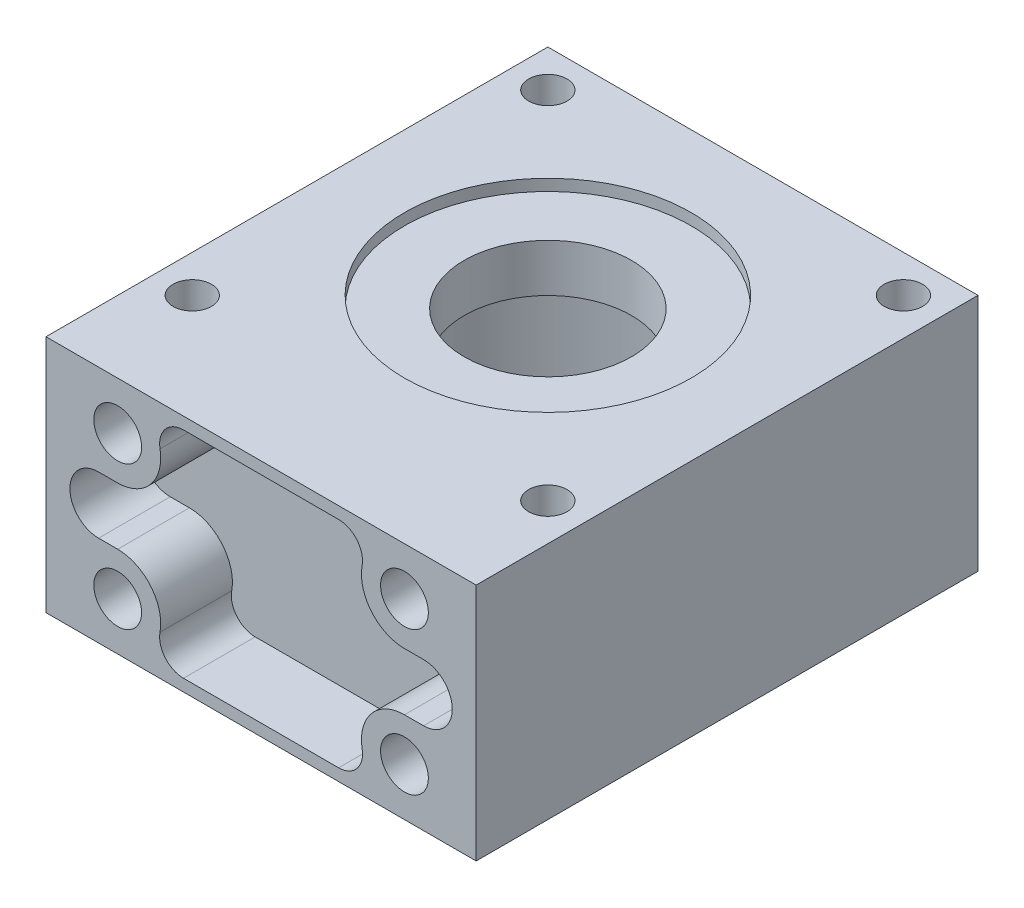
SolidWorks part; units mm, degrees
material "6061 Alloy"
ref_plane "Front" through (0, 0, 0) normal (0, 0, 1) x (1, 0, 0)
ref_plane "Top" through (0, 0, 0) normal (0, 1, 0) x (1, 0, 0)
ref_plane "Right" through (0, 0, 0) normal (1, 0, 0) x (0, 0, -1)
sketch "Sketch1" plane through (0, 0, 0) normal (0, 1, 0) x (1, 0, 0)
  line L0 (28.575, 28.575) -> (-28.575, 28.575)
  line L1 (-28.575, 28.575) -> (28.575, 28.575) construction
  line L2 (-28.575, 28.575) -> (-28.575, -28.575)
  line L3 (-28.575, -28.575) -> (28.575, -28.575) construction
  line L4 (28.575, 28.575) -> (28.575, -28.575)
  line L5 (-28.575, 28.575) -> (28.575, -28.575) construction
  line L6 (-28.575, -28.575) -> (28.575, 28.575) construction
  line L7 (-23.622, 23.622) -> (23.622, 23.622) construction
  line L8 (-23.622, 23.622) -> (-23.622, -23.622) construction
  line L9 (-23.622, -23.622) -> (23.622, -23.622) construction
  line L10 (23.622, 23.622) -> (23.622, -23.622) construction
  line L11 (-23.622, 23.622) -> (23.622, -23.622) construction
  line L12 (-23.622, -23.622) -> (23.622, 23.622) construction
  line L15 (-28.575, -28.575) -> (-28.575, -38.1)
  line L16 (-28.575, -38.1) -> (28.575, -38.1)
  line L17 (28.575, -38.1) -> (28.575, -28.575)
  circle A0 centre (23.622, -23.622) radius 2.5527
  circle A1 centre (23.622, 23.622) radius 2.5527
  circle A2 centre (-23.622, 23.622) radius 2.5527
  circle A3 centre (-23.622, -23.622) radius 2.5527
  point P0 (0, 0)
  point P6 (0, 0)
  dimension "D3" = 5.1054
  dimension "D1" = 57.15
  dimension "D2" = 47.244
  dimension "D4" = 9.525
extrude "Boss-Extrude1" add sketch "Sketch1" along normal blind 31.75
sketch "Sketch2" plane through (0, 31.75, 0) normal (0, 1, 0) x (1, 0, 0)
  circle A0 centre (0, 0) radius 19.05
  dimension "D1" = 38.1
extrude "Cut-Extrude1" cut sketch "Sketch2" against normal blind 1.524
sketch "Sketch3" plane through (0, 30.226, 0) normal (0, 1, 0) x (1, 0, 0)
  circle A0 centre (0, 0) radius 11.1125
  dimension "D1" = 22.225
extrude "Cut-Extrude2" cut sketch "Sketch3" against normal through all
sketch "Sketch4" plane through (0, 0, 0) normal (0, -1, 0) x (1, 0, 0)
  line L0 (0, 0) -> (0, 28.575) construction
  line L2 (0, 0) -> (13.0457, 20.2994) construction
  line L5 (-28.575, 28.575) -> (28.575, 28.575) construction
  circle A0 centre (0, 0) radius 21.844 construction
  circle A1 centre (0, 0) radius 24.13 construction
  arc A2 (0, 20.955) -> (2.8224, 22.6758) centre (0, 24.13) ccw
  arc A3 (11.3291, 17.6285) -> (9.8851, 20.602) centre (13.0457, 20.2994) cw
  arc A4 (2.8224, 22.6758) -> (9.8851, 20.602) centre (6.1542, 20.9592) cw
  arc A5 (11.3291, 17.6285) -> (14.6338, 17.5502) centre (13.0457, 20.2994) ccw
  arc A6 (14.6338, 17.5502) -> (19.4542, 11.9872) centre (16.5086, 14.3048) cw
  arc A7 (19.0613, 8.705) -> (19.4542, 11.9872) centre (21.9494, 10.024) cw
  arc A8 (19.0613, 8.705) -> (21.7991, 6.8525) centre (21.9494, 10.024) ccw
  arc A9 (21.7991, 6.8525) -> (22.8467, -0.4334) centre (21.6217, 3.1087) cw
  arc A10 (20.7417, -2.9822) -> (22.8467, -0.4334) centre (23.8844, -3.4341) cw
  arc A11 (20.7417, -2.9822) -> (22.0433, -6.0208) centre (23.8844, -3.4341) ccw
  arc A12 (22.0433, -6.0208) -> (18.9855, -12.7165) centre (19.87, -9.0743) cw
  arc A13 (15.8367, -13.7226) -> (18.9855, -12.7165) centre (18.2362, -15.8018) cw
  arc A14 (15.8367, -13.7226) -> (15.289, -16.9825) centre (18.2362, -15.8018) ccw
  arc A15 (15.289, -16.9825) -> (9.0966, -20.9621) centre (11.8098, -18.3763) cw
  arc A16 (5.9037, -20.1062) -> (9.0966, -20.9621) centre (6.7982, -23.1526) cw
  arc A17 (5.9037, -20.1062) -> (3.6804, -22.5524) centre (6.7982, -23.1526) ccw
  arc A18 (3.6804, -22.5524) -> (-3.6804, -22.5524) centre (0, -21.844) cw
  arc A19 (-5.9037, -20.1062) -> (-3.6804, -22.5524) centre (-6.7982, -23.1526) cw
  arc A20 (-5.9037, -20.1062) -> (-9.0966, -20.9621) centre (-6.7982, -23.1526) ccw
  arc A21 (-9.0966, -20.9621) -> (-15.289, -16.9825) centre (-11.8098, -18.3763) cw
  arc A22 (-15.8367, -13.7226) -> (-15.289, -16.9825) centre (-18.2362, -15.8018) cw
  arc A23 (-15.8367, -13.7226) -> (-18.9855, -12.7165) centre (-18.2362, -15.8018) ccw
  arc A24 (-18.9855, -12.7165) -> (-22.0433, -6.0208) centre (-19.87, -9.0743) cw
  arc A25 (-20.7417, -2.9822) -> (-22.0433, -6.0208) centre (-23.8844, -3.4341) cw
  arc A26 (-20.7417, -2.9822) -> (-22.8467, -0.4334) centre (-23.8844, -3.4341) ccw
  arc A27 (-22.8467, -0.4334) -> (-21.7991, 6.8525) centre (-21.6217, 3.1087) cw
  arc A28 (-19.0613, 8.705) -> (-21.7991, 6.8525) centre (-21.9494, 10.024) cw
  arc A29 (-19.0613, 8.705) -> (-19.4542, 11.9872) centre (-21.9494, 10.024) ccw
  arc A30 (-19.4542, 11.9872) -> (-14.6338, 17.5502) centre (-16.5086, 14.3048) cw
  arc A31 (-11.3291, 17.6285) -> (-14.6338, 17.5502) centre (-13.0457, 20.2994) cw
  arc A32 (-11.3291, 17.6285) -> (-9.8851, 20.602) centre (-13.0457, 20.2994) ccw
  arc A33 (-9.8851, 20.602) -> (-2.8224, 22.6758) centre (-6.1542, 20.9592) cw
  arc A34 (0, 20.955) -> (-2.8224, 22.6758) centre (0, 24.13) cw
  point P14 (0, 28.575)
  point P87 (0, 0)
  dimension "D1" = 48.26
  dimension "D2" = 43.688
  dimension "D4" = 3.175
  dimension "D5" = 3.175
  dimension "D3" = 32.727
  dimension "D6" = 11
extrude "Cut-Extrude3" cut sketch "Sketch4" against normal blind 23.876
sketch "Sketch5" plane through (0, 0, 0) normal (0, -1, 0) x (1, 0, 0)
  circle A0 centre (0, 0) radius 26.1937
  dimension "D1" = 52.3875
extrude "Cut-Extrude4" cut sketch "Sketch5" against normal blind 17.526
sketch "Sketch7" plane through (0, 0, 0) normal (0, -1, 0) x (1, 0, 0)
  line L0 (-28.575, -28.575) -> (28.575, -28.575) construction
  line L4 (-28.575, -28.575) -> (-28.575, 38.1) construction
  line L5 (-23.8125, 26.9875) -> (23.8125, 26.9875)
  line L6 (-26.9875, 23.8125) -> (-26.9875, -23.8125)
  line L7 (-23.8125, -26.9875) -> (23.8125, -26.9875)
  line L8 (26.9875, 23.8125) -> (26.9875, -23.8125)
  line L9 (-26.9875, 26.9875) -> (26.9875, -26.9875) construction
  line L10 (-26.9875, -26.9875) -> (26.9875, 26.9875) construction
  arc A0 (-26.9875, -23.8125) -> (-23.8125, -26.9875) centre (-23.8125, -23.8125) ccw
  arc A2 (23.8125, -26.9875) -> (26.9875, -23.8125) centre (23.8125, -23.8125) ccw
  arc A3 (23.8125, 26.9875) -> (26.9875, 23.8125) centre (23.8125, 23.8125) cw
  arc A4 (-23.8125, 26.9875) -> (-26.9875, 23.8125) centre (-23.8125, 23.8125) ccw
  point P0 (0, 0)
  dimension "D1" = 1.5875
  dimension "D3" = 3.175
  dimension "D2" = 1.5875
extrude "Cut-Extrude5" cut sketch "Sketch7" against normal blind 1.5875
ref_plane "Plane1" through (0, 0, 28.575) normal (0, 0, 1) x (1, 0, 0)
sketch "Sketch10" plane through (0, 0, 38.1) normal (0, 0, 1) x (1, 0, 0)
  line L0 (28.575, 31.75) -> (28.575, 0) construction
  line L1 (19.05, 25.4) -> (-19.05, 25.4)
  line L2 (19.05, 25.4) -> (19.05, 6.35)
  line L3 (19.05, 6.35) -> (-19.05, 6.35)
  line L4 (-19.05, 25.4) -> (-19.05, 6.35)
  line L5 (19.05, 25.4) -> (-19.05, 6.35) construction
  line L6 (19.05, 6.35) -> (-19.05, 25.4) construction
  line L7 (-28.575, 0) -> (28.575, 0) construction
  point P0 (0, 15.875)
  point P7 (28.575, 15.875)
  point P10 (0, 0)
  dimension "D1" = 38.1
  dimension "D2" = 19.05
hole_wizard "1/4-20 Tapped Hole1" positions "Sketch12" profile "Sketch11" tap size "1/4-20" standard "ANSI Inch"
sketch "Sketch12" plane through (0, 0, 38.1) normal (0, 0, 1) x (1, 0, 0)
  point P0 (-19.05, 25.4)
  point P3 (19.05, 25.4)
  point P6 (19.05, 6.35)
  point P9 (-19.05, 6.35)
sketch "Sketch11" plane through (-19.05, 25.4, 38.1) normal (1, 0, 0) x (0, -1, 0)
  line L0 (0, 0) -> (0, 11.1858)
  line L1 (0, 11.1858) -> (2.5527, 9.652)
  line L2 (2.5527, 9.652) -> (2.5527, 9.525)
  line L3 (2.5527, 9.525) -> (3.175, 9.525)
  line L4 (3.175, 9.525) -> (3.175, 0)
  line L5 (3.175, 0) -> (0, 0)
  line L10 (0, 11.1858) -> (-2.5527, 9.652) construction
  line L11 (0, -6.35) -> (0, 107.95) construction
  dimension "Tap Drill Dia." = 5.1054
  dimension "Tap Drill Depth" = 9.652
  dimension "Thread Major Dia." = 6.35
  dimension "Thread Depth" = 9.525
  dimension "Drill Angle" = 118
sketch "Sketch13" plane through (0, 0, 38.1) normal (0, 0, 1) x (1, 0, 0)
  line L0 (-28.575, 15.875) -> (0, 15.875) construction
  line L1 (-28.575, 31.75) -> (-28.575, 0) construction
  line L2 (0, 15.875) -> (0, 0) construction
  line L3 (-21.59, 12.065) -> (-19.05, 12.065)
  line L4 (-10.3029, 30.1625) -> (10.3029, 30.1625)
  line L5 (-10.3029, 1.5875) -> (10.3029, 1.5875)
  line L6 (-28.575, 0) -> (28.575, 0) construction
  line L7 (-21.59, 19.685) -> (-19.05, 19.685)
  line L8 (21.59, 12.065) -> (19.05, 12.065)
  line L9 (21.59, 19.685) -> (19.05, 19.685)
  arc A0 (-21.59, 19.685) -> (-21.59, 12.065) centre (-21.59, 15.875) ccw
  arc A1 (-19.05, 12.065) -> (-13.4269, 5.3295) centre (-19.05, 6.35) cw
  arc A2 (-13.4269, 5.3295) -> (-10.3029, 1.5875) centre (-10.3029, 4.7625) ccw
  arc A3 (-13.4269, 26.4205) -> (-10.3029, 30.1625) centre (-10.3029, 26.9875) cw
  arc A4 (-19.05, 19.685) -> (-13.4269, 26.4205) centre (-19.05, 25.4) ccw
  arc A5 (13.4269, 5.3295) -> (10.3029, 1.5875) centre (10.3029, 4.7625) cw
  arc A6 (19.05, 12.065) -> (13.4269, 5.3295) centre (19.05, 6.35) ccw
  arc A7 (21.59, 19.685) -> (21.59, 12.065) centre (21.59, 15.875) cw
  arc A8 (19.05, 19.685) -> (13.4269, 26.4205) centre (19.05, 25.4) cw
  arc A9 (13.4269, 26.4205) -> (10.3029, 30.1625) centre (10.3029, 26.9875) ccw
  point P14 (-25.4, 15.875)
  point P23 (0, 1.5875)
  point P35 (0, 30.1625)
  dimension "D1" = 1.5875
  dimension "D2" = 3.175
  dimension "D3" = 5.715
  dimension "D4" = 3.175
extrude "Cut-Extrude6" cut sketch "Sketch13" against normal offset from surface (9.525 mm away) 1.5875 up to face at (0, 0.7937, 26.9875)
sketch "Sketch14" plane through (0, 0, 28.575) normal (0, 0, 1) x (1, 0, 0)
  line L1 (9.525, 3.1825) -> (-9.525, 3.1825)
  line L2 (12.7, 6.3575) -> (12.7, 25.4075)
  line L3 (9.525, 28.5825) -> (-9.525, 28.5825)
  line L4 (-12.7, 6.3575) -> (-12.7, 25.4075)
  line L5 (12.7, 3.1825) -> (-12.7, 28.5825) construction
  line L6 (12.7, 28.5825) -> (-12.7, 3.1825) construction
  arc A0 (9.525, 3.1825) -> (12.7, 6.3575) centre (9.525, 6.3575) ccw
  arc A1 (-9.525, 3.1825) -> (-12.7, 6.3575) centre (-9.525, 6.3575) cw
  arc A2 (12.7, 25.4075) -> (9.525, 28.5825) centre (9.525, 25.4075) ccw
  arc A3 (-12.7, 25.4075) -> (-9.525, 28.5825) centre (-9.525, 25.4075) cw
  point P0 (0, 15.8825)
  dimension "D2" = 3.175
  dimension "D1" = 25.4
  dimension "D3" = 25.4
